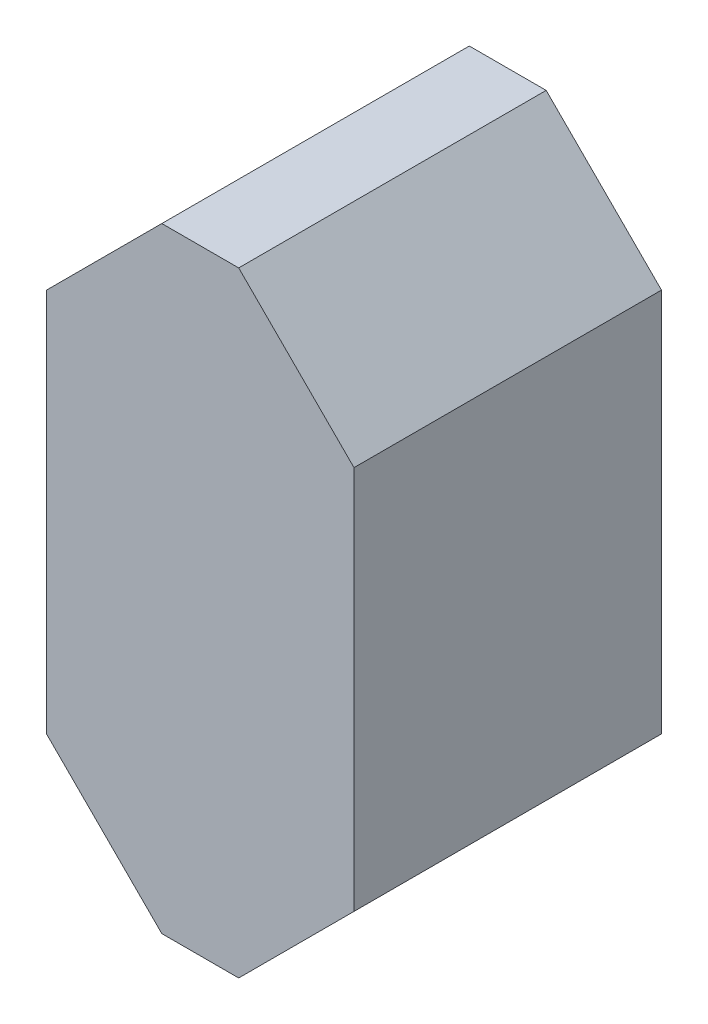
SolidWorks part; units mm, degrees
ref_plane "Front Plane" through (0, 0, 0) normal (0, 0, 1) x (1, 0, 0)
ref_plane "Top Plane" through (0, 0, 0) normal (0, 1, 0) x (1, 0, 0)
ref_plane "Right Plane" through (0, 0, 0) normal (1, 0, 0) x (0, 0, -1)
sketch "Sketch1" plane through (0, 0, 0) normal (0, 0, 1) x (1, 0, 0)
  line L0 (0, 4) -> (0, -4) construction
  line L1 (-2, 4) -> (2, 4)
  line L2 (-2, 4) -> (-2, -4)
  line L3 (-2, -4) -> (2, -4)
  line L4 (2, 4) -> (2, -4)
  line L5 (2, 0) -> (-2, 0) construction
  point P0 (0, 4)
  point P9 (-2, 0)
  dimension "D1" = 4
  dimension "D2" = 8
extrude "Boss-Extrude1" add sketch "Sketch1" along normal blind 4
chamfer "Chamfer1" distance 1.5 distance2 1.5 4 edges at (-2, -4, 2) (2, -4, 2) (-2, 4, 2) (2, 4, 2)
